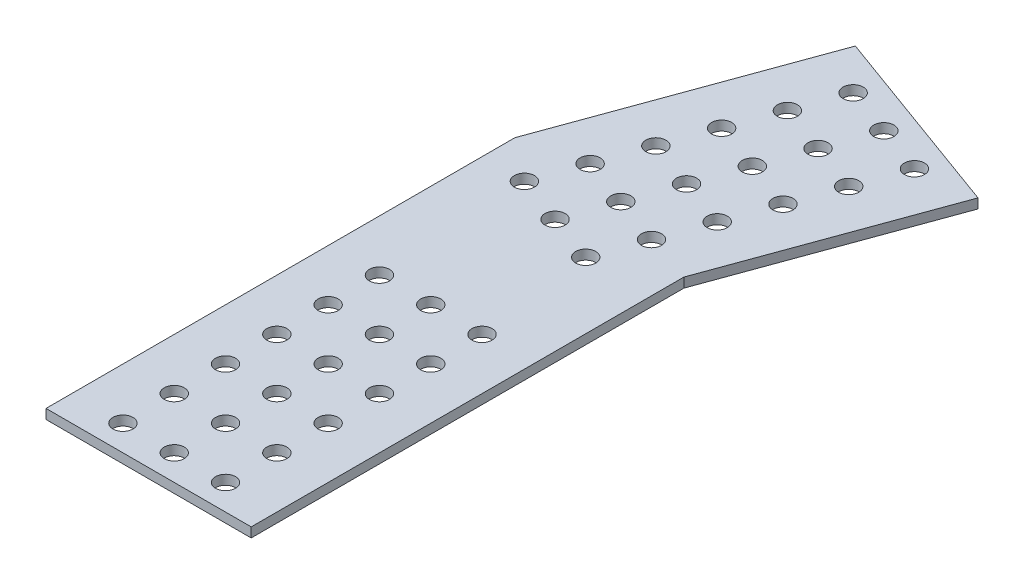
SolidWorks part; units mm, degrees
ref_plane "Front Plane" through (0, 0, 0) normal (0, 0, 1) x (1, 0, 0)
ref_plane "Top Plane" through (0, 0, 0) normal (0, 1, 0) x (1, 0, 0)
ref_plane "Right Plane" through (0, 0, 0) normal (1, 0, 0) x (0, 0, -1)
sketch "Sketch1" plane through (0, 0, 0) normal (0, 1, 0) x (1, 0, 0)
  line L0 (-80.3795, -295.1056) -> (-128.1159, -277.731) construction
  line L1 (-80.3795, -295.1056) -> (128.1159, 277.731) construction
  line L2 (-124.5455, -267.9214) -> (80.3795, 295.1056) construction
  line L3 (128.1159, 277.731) -> (80.3795, 295.1056) construction
  line L4 (-80.3795, -295.1056) -> (80.3795, 295.1056) construction
  line L5 (-128.1159, -277.731) -> (128.1159, 277.731) construction
  line L6 (104.2477, 286.4183) -> (-104.2477, -286.4183) construction
  line L7 (-73.7455, -307.8056) -> (-124.5455, -307.8056)
  line L8 (-73.7455, -307.8056) -> (-73.7455, -422.1056) construction
  line L9 (-73.7455, -422.1056) -> (-124.5455, -422.1056) construction
  line L10 (-124.5455, -307.8056) -> (-124.5455, -422.1056) construction
  line L11 (-99.1455, -307.8056) -> (-99.1455, -422.1056) construction
  line L12 (-105.4955, -307.8056) -> (-105.4955, -422.1056) construction
  line L13 (-99.1455, -307.8056) -> (-99.1455, -288.2754) construction
  line L14 (98.2807, 288.5901) -> (-110.2148, -284.2465) construction
  line L15 (-102.054, -206.1264) -> (-54.3176, -223.501)
  line L16 (-102.054, -206.1264) -> (-124.5455, -267.9214)
  line L19 (-73.7455, -384.0056) -> (-124.5455, -384.0056)
  line L20 (-73.7455, -307.8056) -> (-73.7455, -384.0056)
  line L21 (-124.5455, -307.8056) -> (-124.5455, -384.0056)
  line L22 (-124.5455, -307.8056) -> (-124.5455, -267.9214)
  line L23 (-124.5455, -267.9214) -> (-73.7455, -286.4111)
  line L24 (-73.7455, -307.8056) -> (-73.7455, -286.4111)
  line L26 (-128.1159, -277.731) -> (-124.5455, -307.8056) construction
  line L27 (-73.7455, -286.4111) -> (-73.7455, -276.8788)
  line L28 (-54.3176, -223.501) -> (-73.7455, -276.8788)
  circle A0 centre (-111.8455, -314.1556) radius 2.4892
  circle A1 centre (-111.8455, -326.8556) radius 2.4892
  circle A2 centre (-111.8455, -339.5556) radius 2.4892
  circle A3 centre (-111.8455, -352.2556) radius 2.4892
  circle A4 centre (-111.8455, -364.9556) radius 2.4892
  circle A5 centre (-111.8455, -377.6556) radius 2.4892
  circle A6 centre (-111.8455, -390.3556) radius 2.4892 construction
  circle A7 centre (-111.8455, -403.0556) radius 2.4892 construction
  circle A8 centre (-111.8455, -415.7556) radius 2.4892 construction
  circle A9 centre (-99.1455, -403.0556) radius 2.4892 construction
  circle A10 centre (-99.1455, -390.3556) radius 2.4892 construction
  circle A11 centre (-99.1455, -377.6556) radius 2.4892
  circle A12 centre (-99.1455, -364.9556) radius 2.4892
  circle A13 centre (-99.1455, -352.2556) radius 2.4892
  circle A14 centre (-99.1455, -339.5556) radius 2.4892
  circle A15 centre (-99.1455, -326.8556) radius 2.4892
  circle A16 centre (-99.1455, -314.1556) radius 2.4892
  circle A17 centre (-86.4455, -415.7556) radius 2.4892 construction
  circle A18 centre (-86.4455, -403.0556) radius 2.4892 construction
  circle A19 centre (-86.4455, -390.3556) radius 2.4892 construction
  circle A20 centre (-86.4455, -377.6556) radius 2.4892
  circle A21 centre (-86.4455, -364.9556) radius 2.4892
  circle A22 centre (-86.4455, -352.2556) radius 2.4892
  circle A23 centre (-86.4455, -339.5556) radius 2.4892
  circle A24 centre (-86.4455, -326.8556) radius 2.4892
  circle A25 centre (-86.4455, -314.1556) radius 2.4892
  circle A26 centre (-99.1455, -415.7556) radius 2.4892 construction
  circle A27 centre (90.1418, 284.7949) radius 2.4892 construction
  circle A28 centre (85.7982, 272.8608) radius 2.4892 construction
  circle A29 centre (81.4545, 260.9267) radius 2.4892 construction
  circle A30 centre (77.1108, 248.9926) radius 2.4892 construction
  circle A31 centre (72.7672, 237.0585) radius 2.4892 construction
  circle A32 centre (68.4235, 225.1244) radius 2.4892 construction
  circle A33 centre (64.0799, 213.1903) radius 2.4892 construction
  circle A34 centre (59.7362, 201.2562) radius 2.4892 construction
  circle A35 centre (55.3926, 189.3221) radius 2.4892 construction
  circle A36 centre (51.0489, 177.3881) radius 2.4892 construction
  circle A37 centre (46.7053, 165.454) radius 2.4892 construction
  circle A38 centre (42.3616, 153.5199) radius 2.4892 construction
  circle A39 centre (38.0179, 141.5858) radius 2.4892 construction
  circle A40 centre (33.6743, 129.6517) radius 2.4892 construction
  circle A41 centre (29.3306, 117.7176) radius 2.4892 construction
  circle A42 centre (24.987, 105.7835) radius 2.4892 construction
  circle A43 centre (20.6433, 93.8494) radius 2.4892 construction
  circle A44 centre (16.2997, 81.9153) radius 2.4892 construction
  circle A45 centre (11.956, 69.9812) radius 2.4892 construction
  circle A46 centre (7.6124, 58.0471) radius 2.4892 construction
  circle A47 centre (3.2687, 46.113) radius 2.4892 construction
  circle A48 centre (-1.075, 34.1789) radius 2.4892 construction
  circle A49 centre (-5.4186, 22.2448) radius 2.4892 construction
  circle A50 centre (-9.7623, 10.3107) radius 2.4892 construction
  circle A51 centre (-14.1059, -1.6234) radius 2.4892 construction
  circle A52 centre (-18.4496, -13.5575) radius 2.4892 construction
  circle A53 centre (-22.7932, -25.4916) radius 2.4892 construction
  circle A54 centre (-27.1369, -37.4257) radius 2.4892 construction
  circle A55 centre (-31.4805, -49.3598) radius 2.4892 construction
  circle A56 centre (-35.8242, -61.2939) radius 2.4892 construction
  circle A57 centre (-40.1679, -73.228) radius 2.4892 construction
  circle A58 centre (-44.5115, -85.1621) radius 2.4892 construction
  circle A59 centre (-48.8552, -97.0962) radius 2.4892 construction
  circle A60 centre (-53.1988, -109.0303) radius 2.4892 construction
  circle A61 centre (-57.5425, -120.9644) radius 2.4892 construction
  circle A62 centre (-61.8861, -132.8985) radius 2.4892 construction
  circle A63 centre (-66.2298, -144.8325) radius 2.4892 construction
  circle A64 centre (-70.5734, -156.7666) radius 2.4892 construction
  circle A65 centre (-74.9171, -168.7007) radius 2.4892 construction
  circle A66 centre (-79.2608, -180.6348) radius 2.4892 construction
  circle A67 centre (-83.6044, -192.5689) radius 2.4892 construction
  circle A68 centre (-87.9481, -204.503) radius 2.4892 construction
  circle A69 centre (-92.2917, -216.4371) radius 2.4892
  circle A70 centre (-96.6354, -228.3712) radius 2.4892
  circle A71 centre (-100.979, -240.3053) radius 2.4892
  circle A72 centre (-105.3227, -252.2394) radius 2.4892
  circle A73 centre (-109.6664, -264.1735) radius 2.4892
  circle A74 centre (-114.01, -276.1076) radius 2.4892
  circle A75 centre (62.983, 173.0444) radius 2.4892 construction
  circle A76 centre (67.3267, 184.9785) radius 2.4892 construction
  circle A77 centre (71.6703, 196.9126) radius 2.4892 construction
  circle A78 centre (76.014, 208.8467) radius 2.4892 construction
  circle A79 centre (80.3576, 220.7808) radius 2.4892 construction
  circle A80 centre (84.7013, 232.7149) radius 2.4892 construction
  circle A81 centre (89.0449, 244.649) radius 2.4892 construction
  circle A82 centre (93.3886, 256.5831) radius 2.4892 construction
  circle A83 centre (97.7323, 268.5172) radius 2.4892 construction
  circle A84 centre (102.0759, 280.4513) radius 2.4892 construction
  circle A85 centre (-102.0759, -280.4513) radius 2.4892
  circle A86 centre (-97.7323, -268.5172) radius 2.4892
  circle A87 centre (-93.3886, -256.5831) radius 2.4892
  circle A88 centre (-89.0449, -244.649) radius 2.4892
  circle A89 centre (-84.7013, -232.7149) radius 2.4892
  circle A90 centre (-80.3576, -220.7808) radius 2.4892
  circle A91 centre (-76.014, -208.8467) radius 2.4892 construction
  circle A92 centre (-71.6703, -196.9126) radius 2.4892 construction
  circle A93 centre (-67.3267, -184.9785) radius 2.4892 construction
  circle A94 centre (-62.983, -173.0444) radius 2.4892 construction
  circle A95 centre (-58.6394, -161.1103) radius 2.4892 construction
  circle A96 centre (-54.2957, -149.1762) radius 2.4892 construction
  circle A97 centre (-49.952, -137.2421) radius 2.4892 construction
  circle A98 centre (-45.6084, -125.308) radius 2.4892 construction
  circle A99 centre (-41.2647, -113.3739) radius 2.4892 construction
  circle A100 centre (-36.9211, -101.4398) radius 2.4892 construction
  circle A101 centre (-32.5774, -89.5057) radius 2.4892 construction
  circle A102 centre (-28.2338, -77.5716) radius 2.4892 construction
  circle A103 centre (-23.8901, -65.6375) radius 2.4892 construction
  circle A104 centre (-19.5465, -53.7034) radius 2.4892 construction
  circle A105 centre (-15.2028, -41.7693) radius 2.4892 construction
  circle A106 centre (-10.8591, -29.8352) radius 2.4892 construction
  circle A107 centre (-6.5155, -17.9011) radius 2.4892 construction
  circle A108 centre (-2.1718, -5.967) radius 2.4892 construction
  circle A109 centre (2.1718, 5.967) radius 2.4892 construction
  circle A110 centre (6.5155, 17.9011) radius 2.4892 construction
  circle A111 centre (10.8591, 29.8352) radius 2.4892 construction
  circle A112 centre (15.2028, 41.7693) radius 2.4892 construction
  circle A113 centre (19.5465, 53.7034) radius 2.4892 construction
  circle A114 centre (23.8901, 65.6375) radius 2.4892 construction
  circle A115 centre (28.2338, 77.5716) radius 2.4892 construction
  circle A116 centre (32.5774, 89.5057) radius 2.4892 construction
  circle A117 centre (36.9211, 101.4398) radius 2.4892 construction
  circle A118 centre (41.2647, 113.3739) radius 2.4892 construction
  circle A119 centre (45.6084, 125.308) radius 2.4892 construction
  circle A120 centre (49.952, 137.2421) radius 2.4892 construction
  circle A121 centre (54.2957, 149.1762) radius 2.4892 construction
  circle A122 centre (58.6394, 161.1103) radius 2.4892 construction
  circle A123 centre (-90.1418, -284.7949) radius 2.4892
  circle A124 centre (-85.7982, -272.8608) radius 2.4892
  circle A125 centre (-81.4545, -260.9267) radius 2.4892
  circle A126 centre (-77.1108, -248.9926) radius 2.4892
  circle A127 centre (-72.7672, -237.0585) radius 2.4892
  circle A128 centre (-68.4235, -225.1244) radius 2.4892
  circle A129 centre (-64.0799, -213.1903) radius 2.4892 construction
  circle A130 centre (-59.7362, -201.2562) radius 2.4892 construction
  circle A131 centre (-55.3926, -189.3221) radius 2.4892 construction
  circle A132 centre (-51.0489, -177.3881) radius 2.4892 construction
  circle A133 centre (-46.7053, -165.454) radius 2.4892 construction
  circle A134 centre (-42.3616, -153.5199) radius 2.4892 construction
  circle A135 centre (-38.0179, -141.5858) radius 2.4892 construction
  circle A136 centre (-33.6743, -129.6517) radius 2.4892 construction
  circle A137 centre (-29.3306, -117.7176) radius 2.4892 construction
  circle A138 centre (-24.987, -105.7835) radius 2.4892 construction
  circle A139 centre (-20.6433, -93.8494) radius 2.4892 construction
  circle A140 centre (-16.2997, -81.9153) radius 2.4892 construction
  circle A141 centre (-11.956, -69.9812) radius 2.4892 construction
  circle A142 centre (-7.6124, -58.0471) radius 2.4892 construction
  circle A143 centre (-3.2687, -46.113) radius 2.4892 construction
  circle A144 centre (1.075, -34.1789) radius 2.4892 construction
  circle A145 centre (5.4186, -22.2448) radius 2.4892 construction
  circle A146 centre (9.7623, -10.3107) radius 2.4892 construction
  circle A147 centre (14.1059, 1.6234) radius 2.4892 construction
  circle A148 centre (18.4496, 13.5575) radius 2.4892 construction
  circle A149 centre (22.7932, 25.4916) radius 2.4892 construction
  circle A150 centre (27.1369, 37.4257) radius 2.4892 construction
  circle A151 centre (31.4805, 49.3598) radius 2.4892 construction
  circle A152 centre (35.8242, 61.2939) radius 2.4892 construction
  circle A153 centre (40.1679, 73.228) radius 2.4892 construction
  circle A154 centre (44.5115, 85.1621) radius 2.4892 construction
  circle A155 centre (48.8552, 97.0962) radius 2.4892 construction
  circle A156 centre (53.1988, 109.0303) radius 2.4892 construction
  circle A157 centre (57.5425, 120.9644) radius 2.4892 construction
  circle A158 centre (61.8861, 132.8985) radius 2.4892 construction
  circle A159 centre (66.2298, 144.8325) radius 2.4892 construction
  circle A160 centre (70.5734, 156.7666) radius 2.4892 construction
  circle A161 centre (74.9171, 168.7007) radius 2.4892 construction
  circle A162 centre (79.2608, 180.6348) radius 2.4892 construction
  circle A163 centre (83.6044, 192.5689) radius 2.4892 construction
  circle A164 centre (87.9481, 204.503) radius 2.4892 construction
  circle A165 centre (92.2917, 216.4371) radius 2.4892 construction
  circle A166 centre (96.6354, 228.3712) radius 2.4892 construction
  circle A167 centre (100.979, 240.3053) radius 2.4892 construction
  circle A168 centre (105.3227, 252.2394) radius 2.4892 construction
  circle A169 centre (109.6664, 264.1735) radius 2.4892 construction
  circle A170 centre (114.01, 276.1076) radius 2.4892 construction
  point P1 (0, 0)
  dimension "D9" = 4.9784
  dimension "D15" = 4.9784
  dimension "D1" = 50.8
  dimension "D2" = 609.6
  dimension "D3" = 50.8
  dimension "D4" = 114.3
  dimension "D5" = 20
  dimension "D6" = 12.7
  dimension "D7" = 30.2858
  dimension "D8" = 6.35
  dimension "D10" = 6.35
  dimension "D11" = 12.7
  dimension "D13" = 12.7
  dimension "D14" = 6.35
  dimension "D16" = 6.35
  dimension "D17" = 12.7
  dimension "D19" = 12.7
  dimension "D20" = 6.35
  dimension "D21" = 6.35
  dimension "D12" = 9
  dimension "D18" = 48
extrude "Boss-Extrude1" add sketch "Sketch1" along normal blind 2.3813 contours L7 L21 L19 L20 A24 A22 A20 A15 A13 A11 A5 A4 A3 A2 A1 A0 A12 A14 A16 A21 A23 A25 | L7 L24 L23 L22 A85 A74 A123 | L23 L15 L16 A127 A125 A90 A88 A86 A73 A72 A71 A70 A69 A87 A89 A124 A126 A128 region at (-99.1455, 0, 345.9056) region at (-101.6855, 0, 292.472) region at (-98.7807, 0, 276.1639)
